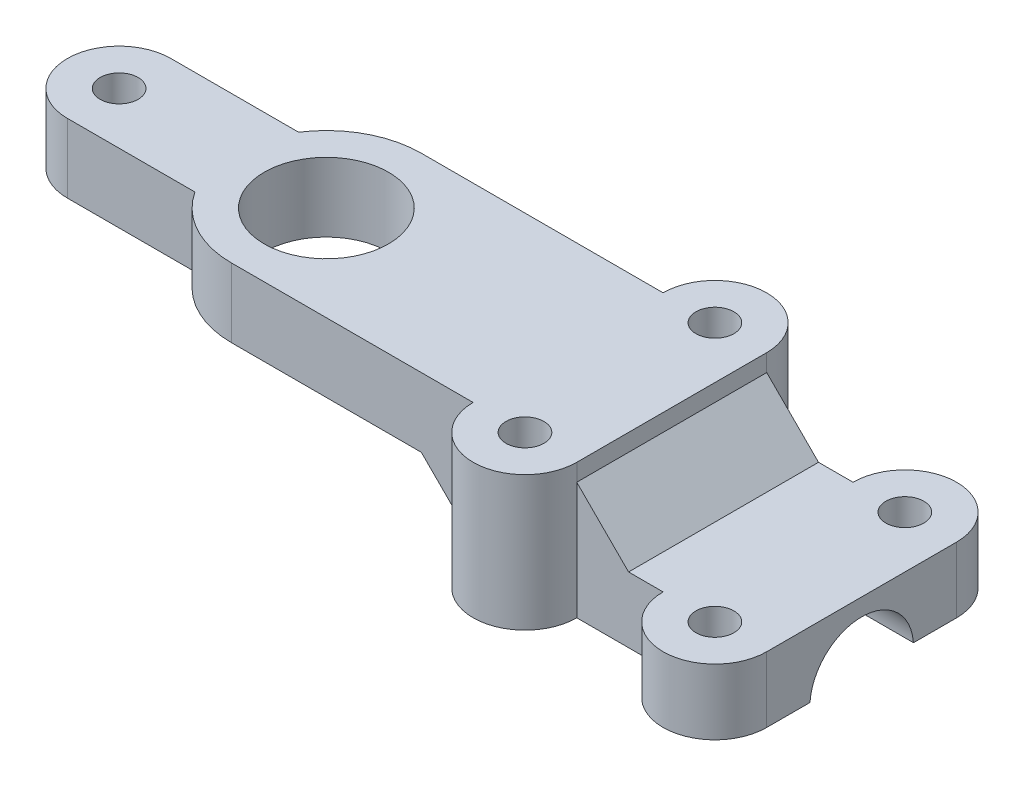
SolidWorks part; units mm, degrees
material "ABS PC"
ref_plane "前视基准面" through (0, 0, 0) normal (0, 0, 1) x (1, 0, 0)
ref_plane "上视基准面" through (0, 0, 0) normal (0, 1, 0) x (1, 0, 0)
ref_plane "右视基准面" through (0, 0, 0) normal (1, 0, 0) x (0, 0, -1)
other "Configuration Table"
sketch "草图1" plane through (0, 0, 0) normal (0, 1, 0) x (1, 0, 0)
  line L0 (0, 0) -> (12, 0) construction
  line L1 (0, 3) -> (7.3902, 3)
  line L2 (0, -3) -> (7.3902, -3)
  line L3 (12, 0) -> (32, 0) construction
  line L4 (12, 5.5) -> (32, 5.5)
  line L5 (32, 5.5) -> (32, -5.5)
  line L6 (12, -5.5) -> (32, -5.5)
  circle A0 centre (0, 0) radius 3
  circle A1 centre (12, 0) radius 5.5
  circle A2 centre (0, 0) radius 1.1
  circle A3 centre (12, 0) radius 3.6
  circle A4 centre (29, 5.5) radius 1.1
  circle A5 centre (29, 5.5) radius 3
  circle A6 centre (29, -5.5) radius 1.1
  circle A7 centre (29, -5.5) radius 3
  dimension "D1" = 6
  dimension "D2" = 11
  dimension "D4" = 2.2
  dimension "D5" = 7.2
  dimension "D8" = 2.2
  dimension "D3" = 12
  dimension "D6" = 20
  dimension "D7" = 3
extrude "凸台-拉伸1" add sketch "草图1" along normal blind 4 contours A0 A2 | A1 L1 A0 L2 | A1 A3 | L6 A7 L5 A5 L4 A1 | L4 A5 A4 | L4 A5 A4 | A7 L6 A6 | A7 L6 A6 region at (4.5284, 0, 0) region at (2.0613, 0, -2.0613) region at (9.4521, 0, -4.698) region at (23.1534, 0, 0) region at (29, 0, -6.8985) region at (29, 0, -4.1015) region at (29, 0, 4.1015) region at (29, 0, 6.8985)
sketch "草图2" plane through (0, 0, 0) normal (0, -1, 0) x (1, 0, 0)
  line L0 (26, 5.5) -> (26, -5.5)
  line L1 (32, 5.5) -> (37, 5.5)
  line L2 (32, 0) -> (43, 0) construction
  line L3 (32, -5.5) -> (32, 5.5) construction
  line L4 (43, 0) -> (43, 5.5)
  line L5 (32, -5.5) -> (37, -5.5)
  line L6 (43, -5.5) -> (43, 0)
  arc A0 (26, -5.5) -> (32, -5.5) centre (29, -5.5) ccw construction
  arc A1 (32, 5.5) -> (26, 5.5) centre (29, 5.5) ccw construction
  circle A2 centre (29, 5.5) radius 1.1 construction
  arc A3 (26, -5.5) -> (32, -5.5) centre (29, -5.5) ccw
  arc A4 (32, 5.5) -> (26, 5.5) centre (29, 5.5) ccw
  circle A5 centre (29, 5.5) radius 1.1
  circle A6 centre (29, -5.5) radius 1.1 construction
  circle A7 centre (29, -5.5) radius 1.1
  arc A8 (43, 5.5) -> (37, 5.5) centre (40, 5.5) ccw
  circle A9 centre (40, 5.5) radius 1.1
  circle A10 centre (40, -5.5) radius 1.1
  arc A11 (43, -5.5) -> (37, -5.5) centre (40, -5.5) cw
  circle M14 centre (29, 5.5) radius 1.1
  circle M15 centre (29, -5.5) radius 1.1
  arc M21 (26, -5.5) -> (32, -5.5) centre (29, -5.5) ccw
  line M22 (32, -5.5) -> (32, 5.5)
  arc M23 (32, 5.5) -> (26, 5.5) centre (29, 5.5) ccw
  dimension "D2" = 6
  dimension "D3" = 8
  dimension "D4" = 2.2
  dimension "D1" = 11
extrude "凸台-拉伸2" add sketch "草图2" along normal blind 4 contours L0 M23 M21 M22 M14 M15 | L2 L4 A8 L1 A9 M22 | L2 L5 A11 L6 A10 M22 region at (29, 0, 0) region at (37.8648, 0, 3.4054) region at (37.8648, 0, -3.4054)
chamfer "倒角1" distance 3 angle 45 2 edges at (32, 0, 0) (26, 0, 0)
sketch "草图3" plane through (43, 0, 0) normal (1, 0, 0) x (0, 0, -1)
  line L0 (5.5, -4) -> (-5.5, -4) construction
  circle A0 centre (0, -4) radius 3
  dimension "D1" = 6
extrude "切除-拉伸1" cut sketch "草图3" against normal blind 12
sketch "草图4" plane through (31, 0, 0) normal (1, 0, 0) x (0, 0, -1)
  line L0 (3, -4) -> (-3, -4) construction
  circle A0 centre (0, -4) radius 1
  dimension "D1" = 2
extrude "切除-拉伸2" cut sketch "草图4" against normal blind 12
chamfer "倒角2" distance 0.2 angle 45 4 edges at (28.5, -4, 1) (28.5, -4, -1) (37, -4, -3) (37, -4, 3)
sketch "草图5" plane through (0, -4, 0) normal (0, -1, 0) x (1, 0, 0)
  line L0 (31, -3.2) -> (31, -1.2) construction
  line L2 (26, -1.2) -> (26, -5.5) construction
  line L3 (32, -5.5) -> (37, -5.5) construction
  line L4 (43, -5.5) -> (43, -3.2) construction
  line L6 (26, 5.5) -> (26, 1.2) construction
  line L8 (31, 1.2) -> (31, 3.2) construction
  line L10 (43, 3.2) -> (43, 5.5) construction
  line L11 (37, 5.5) -> (32, 5.5) construction
  line L12 (26, -0.9742) -> (31, -0.9742) construction
  line L13 (31, 0.9742) -> (26, 0.9742) construction
  line L14 (43, 2.9928) -> (31, 2.9928) construction
  line L15 (31, -2.9928) -> (43, -2.9928) construction
  line L16 (31, -2.9928) -> (31, -1.2)
  line L18 (26, -1.2) -> (26, -5.5)
  line L19 (32, -5.5) -> (37, -5.5)
  line L20 (43, -5.5) -> (43, -3.2)
  line L22 (26, 5.5) -> (26, 1.2)
  line L24 (31, 1.2) -> (31, 2.9928)
  line L26 (43, 3.2) -> (43, 5.5)
  line L27 (37, 5.5) -> (32, 5.5)
  line L28 (26, -0.9742) -> (31, -0.9742)
  line L29 (31, 0.9742) -> (26, 0.9742)
  line L30 (43, 2.9928) -> (31, 2.9928)
  line L31 (31, -2.9928) -> (43, -2.9928)
  line L32 (26, 1.2) -> (26, 0.9742)
  line L33 (31, 1.2) -> (31, 0.9742)
  line L34 (26, -0.9742) -> (26, -1.2)
  line L35 (31, -0.9742) -> (31, -1.2)
  line L36 (43, 3.2) -> (43, 2.9928)
  line L37 (43, -2.9928) -> (43, -3.2)
  arc A0 (26, -5.5) -> (32, -5.5) centre (29, -5.5) ccw construction
  arc A1 (37, -5.5) -> (43, -5.5) centre (40, -5.5) ccw construction
  arc A2 (43, 5.5) -> (37, 5.5) centre (40, 5.5) ccw construction
  arc A3 (32, 5.5) -> (26, 5.5) centre (29, 5.5) ccw construction
  arc A4 (26, -5.5) -> (32, -5.5) centre (29, -5.5) ccw
  arc A5 (37, -5.5) -> (43, -5.5) centre (40, -5.5) ccw
  arc A6 (43, 5.5) -> (37, 5.5) centre (40, 5.5) ccw
  arc A7 (32, 5.5) -> (26, 5.5) centre (29, 5.5) ccw
extrude "切除-拉伸3" cut sketch "草图5" against normal blind 0.2
